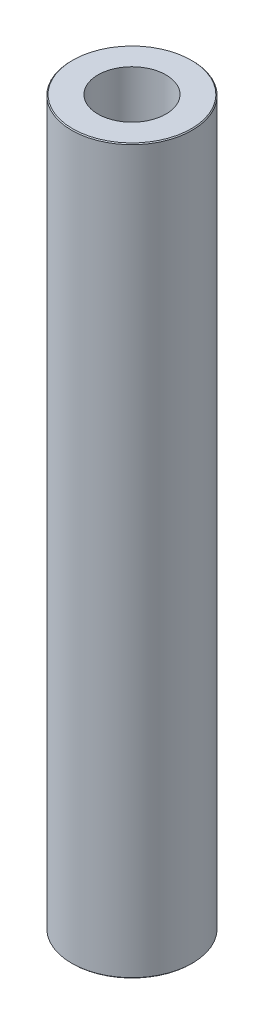
SolidWorks part; units mm, degrees
ref_plane "Front Plane" through (0, 0, 0) normal (0, 0, 1) x (1, 0, 0)
ref_plane "Top Plane" through (0, 0, 0) normal (0, 1, 0) x (1, 0, 0)
ref_plane "Right Plane" through (0, 0, 0) normal (1, 0, 0) x (0, 0, -1)
sketch "Sketch1" plane through (0, 0, 0) normal (0, 1, 0) x (1, 0, 0)
  circle A0 centre (0, 0) radius 50
  dimension "SHAFT_OD" = 100
extrude "Boss-Extrude1" add sketch "Sketch1" along normal blind 600
sketch "Sketch2" plane through (0, 0, 0) normal (0, 1, 0) x (1, 0, 0)
  circle A0 centre (0, 0) radius 28.2096
  dimension "BORE_D" = 56.4191
extrude "Cut-Extrude1" cut sketch "Sketch2" along normal through all
chamfer "Chamfer1" distance 0.7484 angle 45 2 edges at (0, 600, 50) (0, 0, 50)
